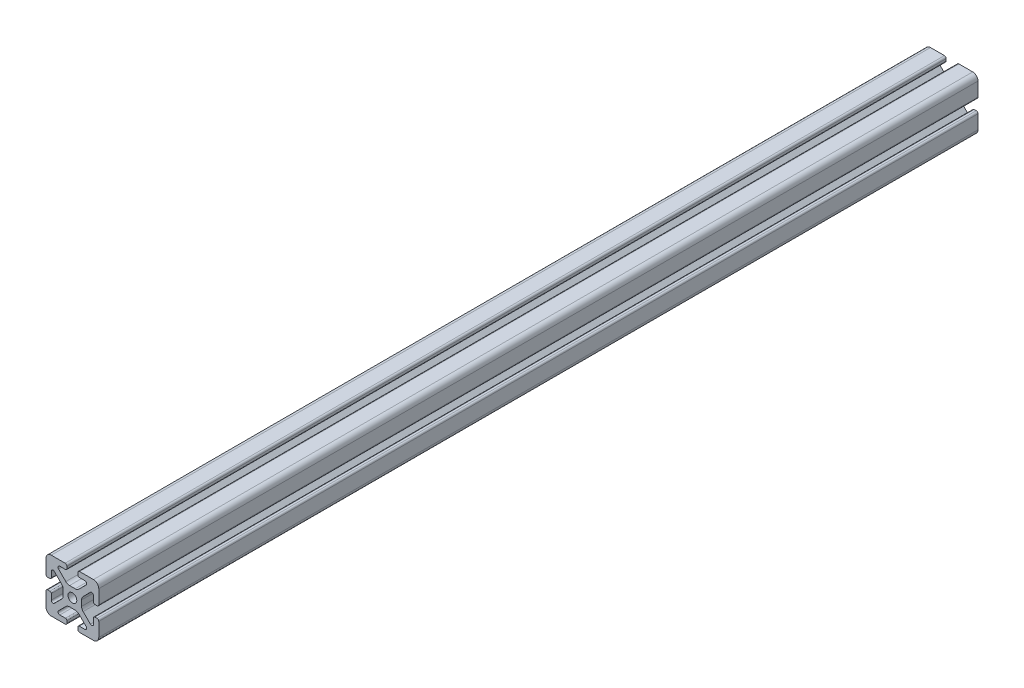
SolidWorks part; units mm, degrees
material "3003 Alloy"
ref_plane "Front Plane" through (0, 0, 0) normal (0, 0, 1) x (1, 0, 0)
ref_plane "Top Plane" through (0, 0, 0) normal (0, 1, 0) x (1, 0, 0)
ref_plane "Right Plane" through (0, 0, 0) normal (1, 0, 0) x (0, 0, -1)
sketch "Sketch1" plane through (0, 0, 0) normal (0, 0, 1) x (1, 0, 0)
  line B0 (1.6032, 5.25) -> (-1.6032, 5.25)
  arc B1 (-12, 15) -> (-15, 12) centre (-12, 12) ccw
  line B2 (-7.1276, 12) -> (-3.9, 12)
  line B3 (7.8506, 10.2547) -> (3.7245, 6.1287)
  line B4 (-10.2547, 7.8506) -> (-6.1287, 3.7245)
  line B5 (3.1, -12.8) -> (3.1, -14)
  arc B6 (3.9, -12) -> (3.1, -12.8) centre (3.9, -12.8) ccw
  line B7 (7.1276, -12) -> (3.9, -12)
  arc B8 (7.1276, -12) -> (7.8506, -10.2547) centre (7.1276, -10.9776) ccw
  line B9 (3.7245, -6.1287) -> (7.8506, -10.2547)
  arc B10 (3.7245, -6.1287) -> (1.6032, -5.25) centre (1.6032, -8.25) ccw
  line B11 (-1.6032, -5.25) -> (1.6032, -5.25)
  arc B12 (-1.6032, -5.25) -> (-3.7245, -6.1287) centre (-1.6032, -8.25) ccw
  line B13 (-7.8506, -10.2547) -> (-3.7245, -6.1287)
  arc B14 (-7.8506, -10.2547) -> (-7.1276, -12) centre (-7.1276, -10.9776) ccw
  line B15 (-3.9, -12) -> (-7.1276, -12)
  arc B16 (-3.1, -12.8) -> (-3.9, -12) centre (-3.9, -12.8) ccw
  line B17 (-3.1, -14) -> (-3.1, -12.8)
  arc B18 (-4.1, -15) -> (-3.1, -14) centre (-4.1, -14) ccw
  line B19 (-12, -15) -> (-4.1, -15)
  arc B20 (-15, -12) -> (-12, -15) centre (-12, -12) ccw
  line B21 (-15, -4.1) -> (-15, -12)
  arc B22 (-14, -3.1) -> (-15, -4.1) centre (-14, -4.1) ccw
  line B23 (-12.8, -3.1) -> (-14, -3.1)
  arc B24 (-12, -3.9) -> (-12.8, -3.1) centre (-12.8, -3.9) ccw
  line B25 (-12, -7.1276) -> (-12, -3.9)
  arc B26 (-12, -7.1276) -> (-10.2547, -7.8506) centre (-10.9776, -7.1276) ccw
  line B27 (-6.1287, -3.7245) -> (-10.2547, -7.8506)
  arc B28 (-6.1287, -3.7245) -> (-5.25, -1.6032) centre (-8.25, -1.6032) ccw
  line B29 (-5.25, 1.6032) -> (-5.25, -1.6032)
  arc B30 (-5.25, 1.6032) -> (-6.1287, 3.7245) centre (-8.25, 1.6032) ccw
  arc B31 (-10.2547, 7.8506) -> (-12, 7.1276) centre (-10.9776, 7.1276) ccw
  line B32 (-12, 3.9) -> (-12, 7.1276)
  arc B33 (-12.8, 3.1) -> (-12, 3.9) centre (-12.8, 3.9) ccw
  line B34 (-14, 3.1) -> (-12.8, 3.1)
  arc B35 (-15, 4.1) -> (-14, 3.1) centre (-14, 4.1) ccw
  line B36 (-15, 12) -> (-15, 4.1)
  line B37 (-4.1, 15) -> (-12, 15)
  arc B38 (-3.1, 14) -> (-4.1, 15) centre (-4.1, 14) ccw
  line B39 (-3.1, 12.8) -> (-3.1, 14)
  arc B40 (-3.9, 12) -> (-3.1, 12.8) centre (-3.9, 12.8) ccw
  arc B41 (-7.1276, 12) -> (-7.8506, 10.2547) centre (-7.1276, 10.9776) ccw
  line B42 (-3.7245, 6.1287) -> (-7.8506, 10.2547)
  arc B43 (-3.7245, 6.1287) -> (-1.6032, 5.25) centre (-1.6032, 8.25) ccw
  arc B44 (1.6032, 5.25) -> (3.7245, 6.1287) centre (1.6032, 8.25) ccw
  arc B45 (7.8506, 10.2547) -> (7.1276, 12) centre (7.1276, 10.9776) ccw
  line B46 (3.9, 12) -> (7.1276, 12)
  arc B47 (3.1, 12.8) -> (3.9, 12) centre (3.9, 12.8) ccw
  line B48 (3.1, 14) -> (3.1, 12.8)
  arc B49 (4.1, 15) -> (3.1, 14) centre (4.1, 14) ccw
  line B50 (12, 15) -> (4.1, 15)
  arc B51 (15, 12) -> (12, 15) centre (12, 12) ccw
  line B52 (15, 4.1) -> (15, 12)
  arc B53 (14, 3.1) -> (15, 4.1) centre (14, 4.1) ccw
  line B54 (12.8, 3.1) -> (14, 3.1)
  arc B55 (12, 3.9) -> (12.8, 3.1) centre (12.8, 3.9) ccw
  line B56 (12, 7.1276) -> (12, 3.9)
  arc B57 (12, 7.1276) -> (10.2547, 7.8506) centre (10.9776, 7.1276) ccw
  line B58 (6.1287, 3.7245) -> (10.2547, 7.8506)
  arc B59 (6.1287, 3.7245) -> (5.25, 1.6032) centre (8.25, 1.6032) ccw
  line B60 (5.25, -1.6032) -> (5.25, 1.6032)
  arc B61 (5.25, -1.6032) -> (6.1287, -3.7245) centre (8.25, -1.6032) ccw
  line B62 (10.2547, -7.8506) -> (6.1287, -3.7245)
  arc B63 (10.2547, -7.8506) -> (12, -7.1276) centre (10.9776, -7.1276) ccw
  line B64 (12, -3.9) -> (12, -7.1276)
  arc B65 (12.8, -3.1) -> (12, -3.9) centre (12.8, -3.9) ccw
  line B66 (14, -3.1) -> (12.8, -3.1)
  arc B67 (15, -4.1) -> (14, -3.1) centre (14, -4.1) ccw
  line B68 (15, -12) -> (15, -4.1)
  arc B69 (12, -15) -> (15, -12) centre (12, -12) ccw
  line B70 (4.1, -15) -> (12, -15)
  arc B71 (3.1, -14) -> (4.1, -15) centre (4.1, -14) ccw
  circle B72 centre (0, 0) radius 2.5
sketch_block_instance "IR 30X30 IR41901-2"
sketch_block "IR 30X30 IR41901"
extrude "Boss-Extrude1" add sketch "Sketch1" along normal blind 500
